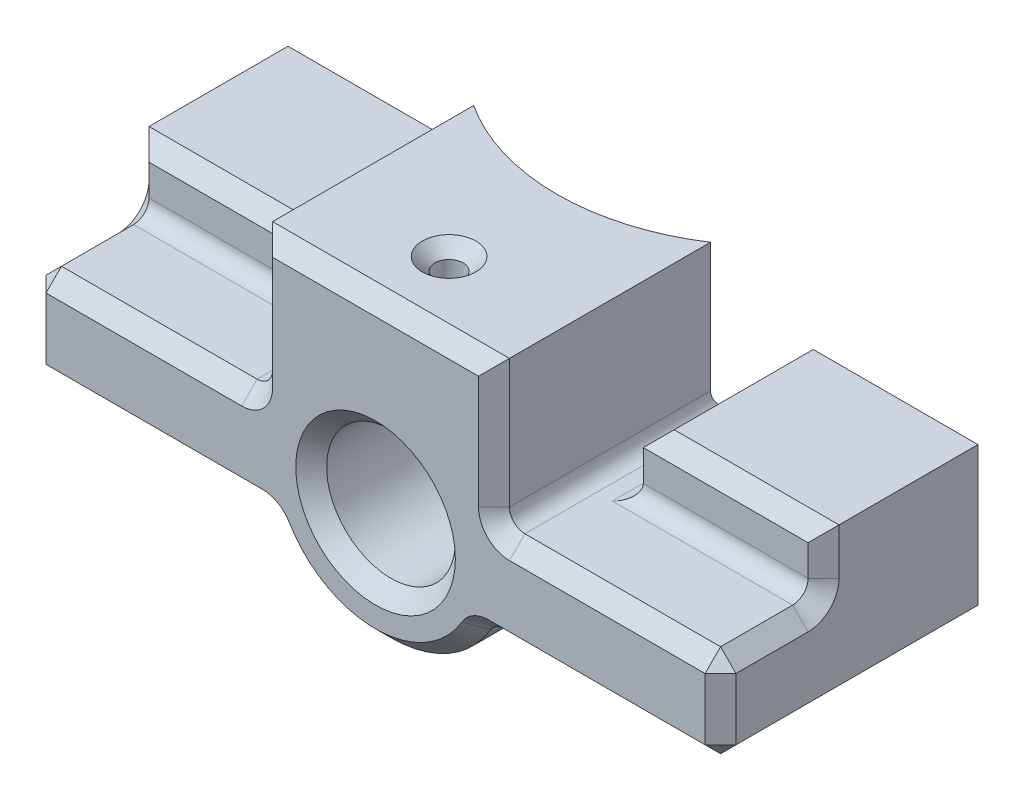
SolidWorks part; units mm, degrees
material "AISI 316 Stainless Steel Sheet (SS)"
ref_plane "Front Plane" through (0, 0, 0) normal (0, 0, 1) x (1, 0, 0)
ref_plane "Top Plane" through (0, 0, 0) normal (0, 1, 0) x (1, 0, 0)
ref_plane "Right Plane" through (0, 0, 0) normal (1, 0, 0) x (0, 0, -1)
sketch "Sketch1" plane through (0, 0, 0) normal (0, 0, 1) x (1, 0, 0)
  line L0 (23, 8) -> (67, 8)
  line L1 (-67, -10) -> (-20.1556, -10)
  line L2 (-67, -10) -> (-67, 8)
  line L3 (-67, 8) -> (-23, 8)
  line L4 (67, -10) -> (67, 8)
  line L5 (20.1556, -10) -> (67, -10)
  line L6 (-23, 8) -> (-23, 36)
  line L7 (-23, 36) -> (23, 36)
  line L8 (23, 36) -> (23, 8)
  circle A0 centre (0, 0) radius 12.5
  arc A1 (-20.1556, -10) -> (20.1556, -10) centre (0, 0) ccw
  point P3 (0, -22.5)
  dimension "D1" = 25
  dimension "D2" = 22.5
  dimension "D3" = 10
  dimension "D4" = 18
  dimension "D5" = 46
  dimension "D6" = 134
  dimension "D7" = 23
  dimension "D8" = 58.5
  dimension "D9" = 44
extrude "Boss-Extrude1" add sketch "Sketch1" against normal blind 50
sketch "Sketch2" plane through (0, -10, 0) normal (0, -1, 0) x (1, 0, 0)
  line L0 (-67, -50) -> (-67, 0) construction
  line L1 (67, -20) -> (32, -20)
  line L2 (67, -20) -> (67, -50)
  line L3 (67, -50) -> (32, -50)
  line L4 (32, -20) -> (32, -50)
  line L5 (-32, -20) -> (-67, -20)
  line L6 (-32, -20) -> (-32, -50)
  line L7 (-32, -50) -> (-67, -50)
  line L8 (-67, -20) -> (-67, -50)
  line L9 (-23, -50) -> (-67, -50) construction
  line L10 (67, -50) -> (23, -50) construction
  line L11 (67, -50) -> (67, 0) construction
  point P8 (-67, -50)
  dimension "D1" = 30
  dimension "D2" = 30
  dimension "D3" = 35
  dimension "D4" = 35
extrude "Boss-Extrude2" add sketch "Sketch2" against normal blind 30
sketch "Sketch3" plane through (0, 0, 0) normal (0, 1, 0) x (1, 0, 0)
  line L0 (-32, 50) -> (-32, 55)
  line L1 (-32, 55) -> (32, 55)
  line L2 (32, 55) -> (32, 50)
  line L3 (23, 50) -> (-23, 50) construction
  arc A0 (-32, 50) -> (32, 50) centre (0, 77.2029) ccw
  dimension "D1" = 42
  dimension "D2" = 5
extrude "Cut-Extrude1" cut sketch "Sketch3" against normal through all both and the other way through all
hole_wizard "Ø5.5 (5.5) Diameter Hole1" positions "Sketch5" profile "Sketch4" hole size "Ø5.5" standard "ANSI Metric" end condition up to next
sketch "Sketch5" plane through (0, 36, 0) normal (0, 1, 0) x (1, 0, 0)
  point P0 (0, 14.2766)
  point P2 (0, 0)
sketch "Sketch4" plane through (0, 36, -14.2766) normal (1, 0, 0) x (0, 0, 1)
  line L0 (0, 0) -> (0, 23.5)
  line L1 (0, 23.5) -> (2.75, 23.5)
  line L2 (2.75, 23.5) -> (2.75, 2.45)
  line L3 (2.75, 2.45) -> (5.2, 0)
  line L5 (5.2, 0) -> (0, 0)
  line L6 (-2.75, 2.45) -> (-5.2, 0) construction
  line L11 (0, -6.35) -> (0, 107.95) construction
  dimension "Thru Hole Dia." = 5.5
  dimension "Thru Hole Depth" = 23.5
  dimension "Near C'Sink Dia." = 10.4
  dimension "Near C'Sink Angle" = 90
fillet "Fillet2" radius 3 8 edges at (49.5, 8, -20) (-49.5, 8, -20) (-32, 8, -35) (32, 8, -35) (23, 8, -21.0302) (-23, 8, -21.0302) (20.1556, -10, -20.1776) (-20.1556, -10, -20.1776)
chamfer "Chamfer1" distance 3 angle 45 27 edges at (12.5, 0, 0) (32, 20, -35) (49.5, 20, -20) (-32, 20, -35) (-49.5, 20, -20) (67, 15.5, -20) (-67, 15.5, -20) (67, 8.8787, -19.1213) (-67, 8.8787, -19.1213) (-46.5, 8, 0) (-23.8787, 8.8787, 0) (-23, 23.5, 0) (0, 36, 0) (23, 23.5, 0) (23.8787, 8.8787, 0) (46.5, 8, 0) (67, 8, -8.5) (67, -1, 0) (67, -10, -25) (44.4687, -10, 0) (20.4522, -10.3934, 0) (0, -22.5, 0) (-20.4522, -10.3934, 0) (-44.4687, -10, 0) (-67, -10, -25) (-67, -1, 0) (-67, 8, -8.5)
